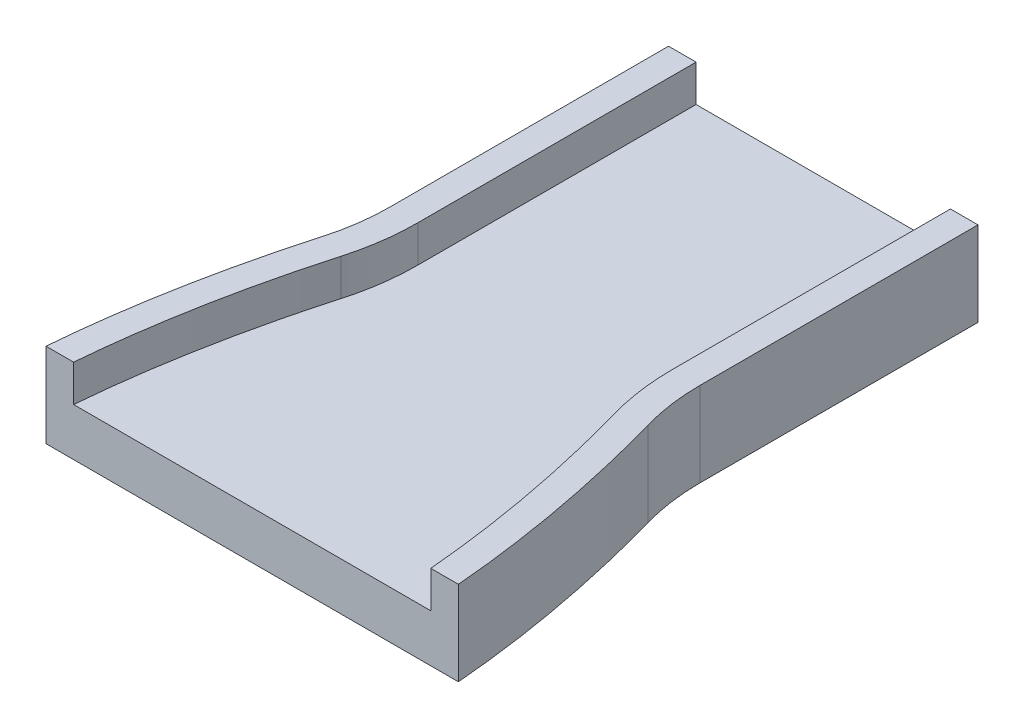
SolidWorks part; units mm, degrees
ref_plane "Alzado" through (0, 0, 0) normal (0, 0, 1) x (1, 0, 0)
ref_plane "Planta" through (0, 0, 0) normal (0, 1, 0) x (1, 0, 0)
ref_plane "Vista lateral" through (0, 0, 0) normal (1, 0, 0) x (0, 0, -1)
sketch "Croquis2" plane through (0, 0, 0) normal (0, 1, 0) x (1, 0, 0)
  line L0 (-34.6199, 80.9973) -> (35.4836, 80.9973)
  line L1 (-49.5506, -74.5192) -> (50.4144, -74.5192)
  line L2 (50.4144, -74.5192) -> (56.5832, -74.5192)
  line L3 (35.4836, 80.9973) -> (42.5674, 80.9973)
  line L4 (42.5674, 80.9973) -> (42.5674, 5.2721)
  line L5 (-49.5506, -74.5192) -> (-55.7195, -74.5192)
  line L6 (-34.6199, 80.9973) -> (-41.7037, 80.9973)
  line L7 (-41.7037, 80.9973) -> (-41.7037, 5.2721)
  arc A0 (44.8459, -11.1055) -> (42.5674, 5.2721) centre (102.5674, 5.2721) cw
  arc A1 (-43.9821, -11.1055) -> (-41.7037, 5.2721) centre (-101.7037, 5.2721) ccw
  spline S0 degree 3 poles (56.5832, -74.5192) (54.897, -53.8979) (50.7074, -31.7639) (44.8459, -11.1055) knots 0 0 0 0 0.769012 0.769012 0.769012 0.769012
  spline S1 degree 3 poles (-55.7195, -74.5192) (-54.0332, -53.8979) (-49.8437, -31.7639) (-43.9821, -11.1055) knots 0 0 0 0 0.769012 0.769012 0.769012 0.769012
  point P10 (0.4319, -74.5192)
  point P17 (0.4319, 80.9973)
  dimension "D1" = 60
extrude "Saliente-Extruir1" add sketch "Croquis2" along normal blind 13 contours L0 L3 L4 A0 S0 L2 L1 L5 S1 A1 L7 L6
sketch "Croquis3" plane through (0, 13, 0) normal (0, 1, 0) x (1, 0, 0)
  line L4 (-55.7195, -74.5192) -> (-48.1937, -74.5192)
  line L5 (-41.7037, 5.2721) -> (-41.7037, 80.9973)
  line L7 (-41.7037, 5.2721) -> (-41.7037, 80.9973)
  line L8 (56.5832, -74.5192) -> (49.0575, -74.5192)
  line L9 (42.5674, 5.2721) -> (42.5674, 80.9973)
  line L10 (42.5674, 5.2721) -> (42.5674, 80.9973)
  line L11 (56.5832, -74.5192) -> (-55.7195, -74.5192) construction
  line L12 (35.0674, 80.9973) -> (42.5674, 80.9973)
  line L13 (-41.7037, 80.9973) -> (-34.2037, 80.9973)
  line L17 (-34.2037, 80.9973) -> (-34.2037, 5.2721)
  line L18 (-34.2037, 80.9973) -> (-34.2037, 5.2721)
  line L22 (35.0674, 80.9973) -> (35.0674, 5.2721)
  line L23 (35.0674, 80.9973) -> (35.0674, 5.2721)
  arc A4 (42.5674, 5.2721) -> (44.8459, -11.1055) centre (102.5674, 5.2721) ccw
  arc A5 (42.5674, 5.2721) -> (44.8459, -11.1055) centre (102.5674, 5.2721) ccw
  arc A6 (-43.9821, -11.1055) -> (-41.7037, 5.2721) centre (-101.7037, 5.2721) ccw
  arc A7 (-43.9821, -11.1055) -> (-41.7037, 5.2721) centre (-101.7037, 5.2721) ccw
  arc A15 (-36.7669, -13.1527) -> (-34.2037, 5.2721) centre (-101.7037, 5.2721) ccw
  arc A16 (-36.7669, -13.1527) -> (-34.2037, 5.2721) centre (-101.7037, 5.2721) ccw
  arc A19 (35.0674, 5.2721) -> (37.6307, -13.1527) centre (102.5674, 5.2721) ccw
  arc A20 (35.0674, 5.2721) -> (37.6307, -13.1527) centre (102.5674, 5.2721) ccw
  spline S4 degree 3 poles (-1773.7885, 3458.4874) (1592.2648, -4644.0882) (-993.1056, 4739.3757) (372.9434, -3982.0495) knots -8.239108 -8.239108 -8.239108 -8.239108 9.323036 9.323036 9.323036 9.323036 only from (56.5832, -74.5192) to (44.8459, -11.1055)
  spline S5 degree 3 poles (56.5832, -74.5192) (54.897, -53.8979) (50.7074, -31.7639) (44.8459, -11.1055) knots 0 0 0 0 0.769012 0.769012 0.769012 0.769012
  spline S7 degree 3 poles (1774.6522, 3458.4874) (-1591.401, -4644.0882) (993.9694, 4739.3757) (-372.0796, -3982.0495) knots -8.239108 -8.239108 -8.239108 -8.239108 9.323036 9.323036 9.323036 9.323036 only from (-55.7195, -74.5192) to (-43.9821, -11.1055)
  spline S8 degree 3 poles (-55.7195, -74.5192) (-54.0332, -53.8979) (-49.8437, -31.7639) (-43.9821, -11.1055) knots 0 0 0 0 0.769012 0.769012 0.769012 0.769012
  spline S11 degree 3 poles (12.2896, -1011.9456) (139.5867, 284.3085) (-13.874, 117.8475) (-72.448, -196.768) (8.4817, -345.6111) (508.2554, 755.7055) knots -7.244544 -7.244544 -7.244544 -7.244544 0.5 0.5 7.791597 7.791597 7.791597 7.791597 only from (-36.7669, -13.1527) to (-48.2444, -75.1305)
  spline S12 degree 3 poles (-36.7669, -13.1527) (-39.6338, -23.2567) (-42.0955, -33.737) (-45.9515, -54.4485) (-47.3662, -64.6812) (-48.1937, -74.5192) knots 0 0 0 0 0.5 0.5 0.989847 0.989847 0.989847 0.989847
  spline S14 degree 3 poles (-11.4259, -1011.9456) (-138.723, 284.3085) (14.7378, 117.8475) (73.3117, -196.768) (-7.6179, -345.6111) (-507.3916, 755.7055) knots -7.244544 -7.244544 -7.244544 -7.244544 0.5 0.5 7.791597 7.791597 7.791597 7.791597 only from (37.6307, -13.1527) to (49.1082, -75.1305)
  spline S15 degree 3 poles (37.6307, -13.1527) (40.4975, -23.2567) (42.9592, -33.737) (46.8152, -54.4485) (48.23, -64.6812) (49.0575, -74.5192) knots 0 0 0 0 0.5 0.5 0.989847 0.989847 0.989847 0.989847
  dimension "D3" = 7.5257
  dimension "D6" = 7.5257
  dimension "D1" = 7.5
  dimension "D2" = 7.5
  dimension "D4" = 0
  dimension "D5" = 0
extrude "Saliente-Extruir2" add sketch "Croquis3" along normal blind 10
